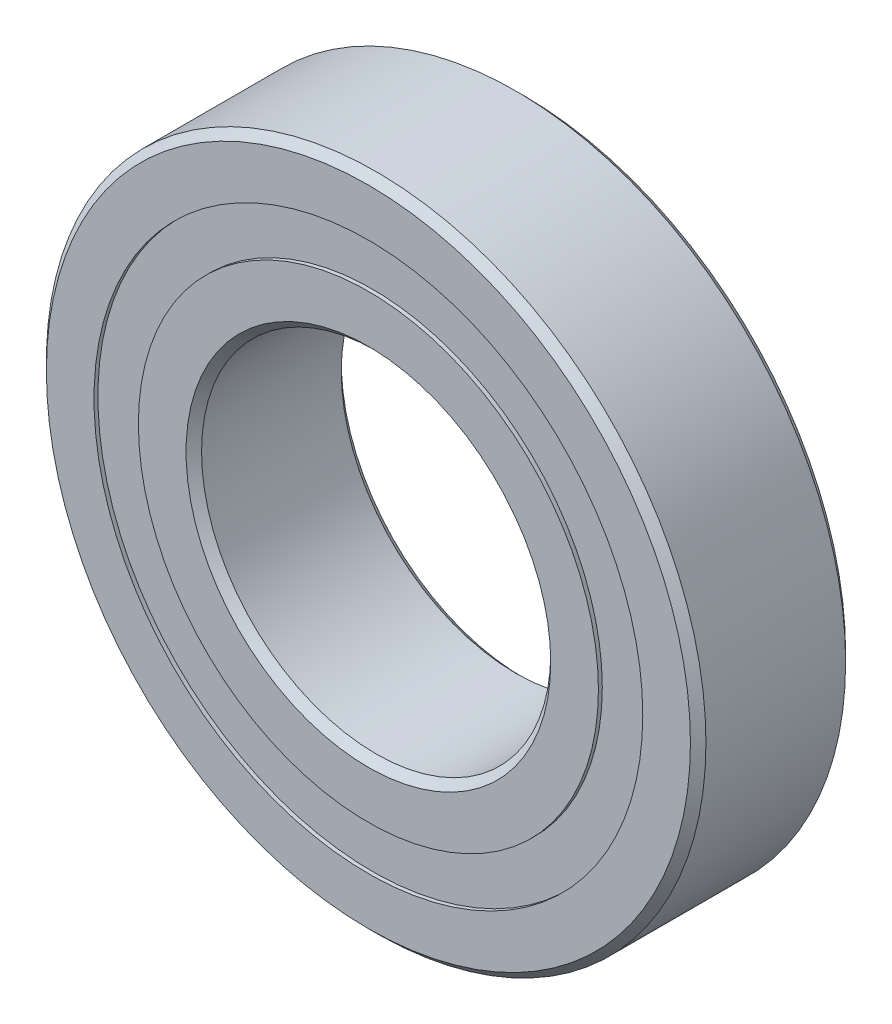
SolidWorks part; units mm, degrees
ref_plane "Front Plane" through (0, 0, 0) normal (0, 0, 1) x (1, 0, 0)
ref_plane "Top Plane" through (0, 0, 0) normal (0, 1, 0) x (1, 0, 0)
ref_plane "Right Plane" through (0, 0, 0) normal (1, 0, 0) x (0, 0, -1)
sketch "Sketch1" plane through (0, 0, 0) normal (1, 0, 0) x (0, 0, -1)
  line L0 (-6.35, 0) -> (6.35, 0) construction
  line L1 (0, 26.9875) -> (0, -26.9875) construction
  line L2 (5.715, 26.9875) -> (-5.715, 26.9875)
  line L3 (-5.715, 26.9875) -> (-6.35, 26.3525)
  line L4 (-6.35, 26.3525) -> (-6.35, 22.4518)
  line L5 (-6.35, 22.4518) -> (-2.8222, 22.4518)
  line L6 (6.35, 22.4518) -> (2.8222, 22.4518)
  line L7 (6.35, 26.3525) -> (6.35, 22.4518)
  line L8 (5.715, 26.9875) -> (6.35, 26.3525)
  line L9 (0, 26.9875) -> (0, 20.6375) construction
  line L10 (0, 20.6375) -> (0, 14.2875) construction
  arc A0 (-2.8222, 22.4518) -> (2.8222, 22.4518) centre (0, 20.6375) cw
  point P14 (0, 14.2875)
  dimension "Width" = 12.7
  dimension "OD" = 53.975
  dimension "D1" = 45
  dimension "D2" = 0.635
  dimension "Shaft Dia" = 28.575
  dimension "D3" = 5.6444
  dimension "D4" = 1.8143
revolve "Revolve1" add sketch "Sketch1" angle 360 about L0
sketch "Sketch3" plane through (0, 0, 0) normal (1, 0, 0) x (0, 0, -1)
  line L0 (-6.35, 18.8232) -> (-2.8222, 18.8232)
  line L1 (0, 26.9875) -> (0, -26.9875) construction
  line L2 (-6.35, 26.3525) -> (-6.35, 22.4518) construction
  line L3 (-6.35, 18.8232) -> (-6.35, 14.9225)
  line L4 (-5.715, 26.9875) -> (-6.35, 26.3525) construction
  line L5 (-6.35, 14.9225) -> (-5.715, 14.2875)
  line L6 (-5.715, 14.2875) -> (5.715, 14.2875)
  line L7 (5.715, 26.9875) -> (5.715, -26.9875) construction
  line L8 (5.715, 14.2875) -> (6.35, 14.9225)
  line L9 (6.35, -26.3525) -> (6.35, 26.3525) construction
  line L10 (6.35, 14.9225) -> (6.35, 18.8232)
  line L11 (6.35, 18.8232) -> (2.8222, 18.8232)
  line L13 (5.715, 26.9875) -> (6.35, 26.3525) construction
  arc A0 (2.8222, 22.4518) -> (-2.8222, 22.4518) centre (0, 20.6375) ccw construction
  arc A1 (2.8222, 18.8232) -> (-2.8222, 18.8232) centre (0, 20.6375) cw
revolve "Revolve3" add sketch "Sketch3" angle 360 about L0
sketch "Sketch4" plane through (0, 0, 0) normal (1, 0, 0) x (0, 0, -1)
  line L0 (-3.3551, 20.6375) -> (3.3551, 20.6375)
  arc A2 (-3.3551, 20.6375) -> (3.3551, 20.6375) centre (0, 20.6375) cw
  arc A3 (2.8222, 22.4518) -> (-2.8222, 22.4518) centre (0, 20.6375) ccw construction
revolve "Revolve4" add sketch "Sketch4" angle 360 about L0
ref_axis "Axis1" through (0, 0, -6.35) along (0, 0, 1)
pattern_circular "CirPattern1" count 12 every 30 about axis through (0, 0, -6.35) along (0, 0, 1) of bodies 104
sketch "Sketch5" plane through (0, 0, 0) normal (1, 0, 0) x (0, 0, -1)
  line L0 (-6.35, 22.4518) -> (-2.8222, 22.4518) construction
  line L1 (-6.0325, 22.4518) -> (-3.3551, 22.4518)
  line L2 (-6.0325, 22.4518) -> (-6.0325, 18.8232)
  line L3 (-6.0325, 18.8232) -> (-3.3551, 18.8232)
  line L4 (-3.3551, 22.4518) -> (-3.3551, 18.8232)
  line L5 (-6.35, 18.8232) -> (-2.8222, 18.8232) construction
  line L6 (6.35, 22.4518) -> (2.8222, 22.4518) construction
  line L7 (6.0325, 22.4518) -> (3.3551, 22.4518)
  line L8 (6.0325, 22.4518) -> (6.0325, 18.8232)
  line L9 (6.0325, 18.8232) -> (3.3551, 18.8232)
  line L10 (3.3551, 22.4518) -> (3.3551, 18.8232)
  line L11 (6.35, 18.8232) -> (2.8222, 18.8232) construction
  line L12 (-5.715, 26.9875) -> (-6.35, 26.3525) construction
  point P18 (-6.0325, 26.67)
revolve "Revolve5" add sketch "Sketch5" angle 360 about L0
equation "\"D2@Sketch1\" = \"Width@Sketch1\"*.05"
equation "\"D3@Sketch1\" = \"Width@Sketch1\"/2.25"
equation "\"D4@Sketch1\" = (((\"OD@Sketch1\"-\"Width@Sketch1\")/2)/3.25)/3.5"
equation "\"D2@CirPattern1\" = 360/\"Balls@CirPattern1\""
